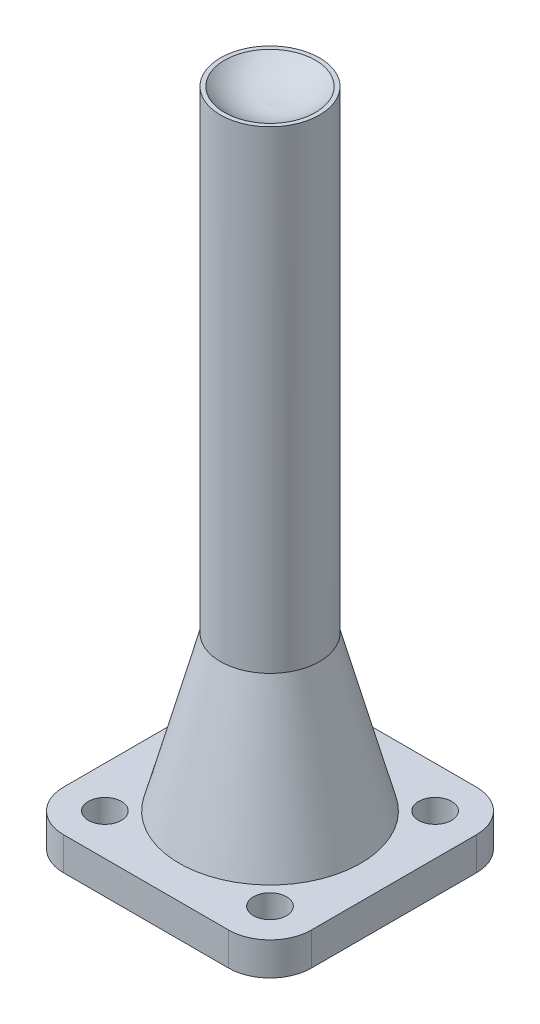
SolidWorks part; units mm, degrees
ref_plane "Спереди" through (0, 0, 0) normal (0, 0, 1) x (1, 0, 0)
ref_plane "Сверху" through (0, 0, 0) normal (0, 1, 0) x (1, 0, 0)
ref_plane "Справа" through (0, 0, 0) normal (1, 0, 0) x (0, 0, -1)
sketch "Эскиз1" plane through (0, 0, 0) normal (0, 1, 0) x (1, 0, 0)
  line L1 (-15, -15) -> (15, -15)
  line L2 (-15, -15) -> (-15, 15)
  line L3 (-15, 15) -> (15, 15)
  line L4 (15, -15) -> (15, 15)
  line L5 (0, 15) -> (0, -15) construction
  line L6 (-15, 0) -> (15, 0) construction
  line L7 (-10, -10) -> (10, -10) construction
  line L8 (-10, -10) -> (-10, 10) construction
  line L9 (-10, 10) -> (10, 10) construction
  line L10 (10, -10) -> (10, 10) construction
  line L11 (0, 10) -> (0, -10) construction
  line L12 (-10, 0) -> (10, 0) construction
  circle A0 centre (-10, 10) radius 2
  circle A1 centre (10, 10) radius 2
  circle A2 centre (10, -10) radius 2
  circle A3 centre (-10, -10) radius 2
  point P0 (0, 0)
  point P4 (0, 0)
  dimension "D5" = 4
  dimension "D1" = 30
  dimension "D2" = 30
  dimension "D3" = 20
  dimension "D4" = 20
extrude "Бобышка-Вытянуть1" add sketch "Эскиз1" along normal blind 4
fillet "Скругление1" radius 5 4 edges at (15, 2, 15) (-15, 2, -15) (15, 2, -15) (-15, 2, 15)
sketch "Эскиз2" plane through (0, 4, 0) normal (0, 1, 0) x (1, 0, 0)
  circle A0 centre (0, 0) radius 6
  dimension "D1" = 12
extrude "Бобышка-Вытянуть2" add sketch "Эскиз2" along normal blind 76
ref_plane "Плоскость1" through (0, 0, 0) normal (0, 0, 1) x (1, 0, 0)
sketch "Эскиз7" plane through (0, 0, 0) normal (0, 0, 1) x (1, 0, 0)
  line L0 (0, 82.4047) -> (0, 78) construction
  line L1 (0, 78) -> (9.0963, 78) construction
  line L2 (6, 80) -> (-6, 80) construction
  line L3 (5.5, 80) -> (0, 80)
  line L4 (0, 80) -> (0, 78)
  arc A0 (0, 78) -> (0.0893, 78) centre (0.0447, 78) ccw
  arc A1 (5.5, 80) -> (0, 78) centre (0.6855, 84.6775) cw
  dimension "D1" = 2
  dimension "D2" = 5.5
revolve "Вырез-Повернуть3" cut sketch "Эскиз7" angle 360 about L0
chamfer "Фаска1" distance 5 angle 75 1 edges at (0, 4, 6) first distance on face at (0, 4, 6)
sketch "Эскиз5" plane through (0, 0, 0) normal (0, -1, 0) x (1, 0, 0)
  line L1 (-16.5147, -16.1651) -> (16.5147, -16.1651)
  line L2 (-16.5147, -16.1651) -> (-16.5147, 16.1651)
  line L3 (-16.5147, 16.1651) -> (16.5147, 16.1651)
  line L4 (16.5147, -16.1651) -> (16.5147, 16.1651)
  line L5 (0, 16.1651) -> (0, -16.1651) construction
  line L6 (-16.5147, 0) -> (16.5147, 0) construction
  point P0 (0, 0)
extrude "Вырез-Вытянуть2" [suppressed] cut sketch "Эскиз5" against normal blind 70
